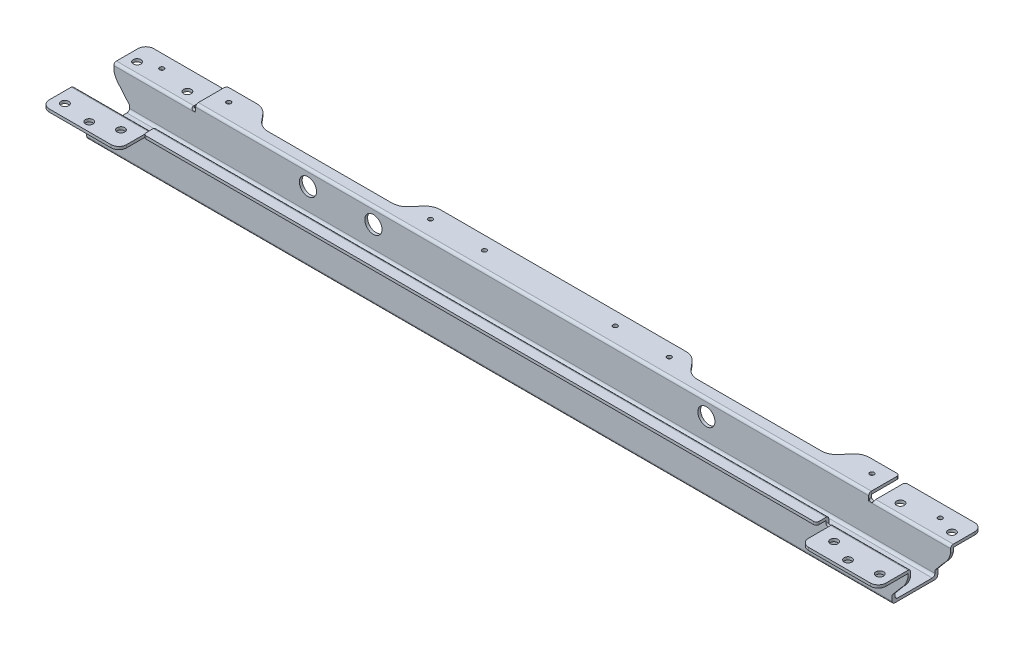
SolidWorks part; units mm, degrees
material "Plain Carbon Steel"
ref_plane "Front Plane" through (0, 0, 0) normal (0, 0, 1) x (1, 0, 0)
ref_plane "Top Plane" through (0, 0, 0) normal (0, 1, 0) x (1, 0, 0)
ref_plane "Right Plane" through (0, 0, 0) normal (1, 0, 0) x (0, 0, -1)
sketch "Sketch1" plane through (0, 0, 0) normal (1, 0, 0) x (0, 0, -1)
  line L0 (-11.095, 0) -> (11.095, 0)
  line L1 (-10.975, 4.55) -> (-10.975, 3)
  line L2 (13.7885, 0) -> (-13.7885, 0) construction
  line L3 (12.535, 1.44) -> (12.535, 4.55)
  line L4 (-12.535, 1.44) -> (-12.535, 4.55)
  line L5 (-12.535, 4.55) -> (-10.975, 4.55)
  line L6 (-9.535, 1.56) -> (9.535, 1.56)
  line L7 (10.975, 3) -> (10.975, 4.55)
  line L8 (10.975, 4.55) -> (12.535, 4.55)
  arc A0 (9.535, 1.56) -> (10.975, 3) centre (9.535, 3) ccw
  arc A1 (11.095, 0) -> (12.535, 1.44) centre (11.095, 1.44) ccw
  arc A2 (-11.095, 0) -> (-12.535, 1.44) centre (-11.095, 1.44) cw
  arc A3 (-10.975, 3) -> (-9.535, 1.56) centre (-9.535, 3) ccw
  point P4 (0, 0)
  point P17 (12.535, 0)
  dimension "D1" = 1.44
  dimension "D5" = 1.56
  dimension "D2" = 25.07
  dimension "D3" = 4.55
  dimension "D4" = 4.55
  dimension "D6" = 1.56
extrude "Boss-Extrude1" add sketch "Sketch1" against normal blind 442.65
sketch "Sketch2" plane through (0, 0, -12.535) normal (0, 0, -1) x (-1, 0, 0)
  line L0 (-8.63, 20.52) -> (-8.63, 16.92)
  line L1 (0, 2.5025) -> (0, -2.5025) construction
  line L2 (406.27, 20.52) -> (406.27, 23.26)
  line L3 (0, 20.52) -> (-8.63, 20.52)
  line L4 (0, 4.55) -> (-4.988, 10.4945)
  line L5 (442.65, 4.55) -> (0, 4.55) construction
  line L6 (0, 20.52) -> (33.94, 20.52)
  line L7 (36.38, 20.52) -> (36.38, 23.26)
  line L8 (36.38, 23.26) -> (406.27, 23.26)
  line L9 (221.325, 23.26) -> (221.325, -129.1352) construction
  line L10 (442.65, 20.52) -> (408.71, 20.52)
  line L11 (442.65, 20.52) -> (451.28, 20.52)
  line L12 (442.65, 4.55) -> (447.638, 10.4945)
  line L13 (451.28, 20.52) -> (451.28, 16.92)
  line L14 (0, 4.55) -> (442.65, 4.55)
  arc A0 (-8.63, 16.92) -> (-4.988, 10.4945) centre (2.9813, 19.2564) ccw
  arc A1 (33.94, 20.52) -> (36.38, 20.52) centre (35.16, 20.52) ccw
  arc A2 (408.71, 20.52) -> (406.27, 20.52) centre (407.49, 20.52) cw
  arc A3 (451.28, 16.92) -> (447.638, 10.4945) centre (439.6687, 19.2564) cw
  dimension "D5" = 11.844
  dimension "D7" = 1.22
  dimension "D1" = 7.76
  dimension "D2" = 3.6
  dimension "D3" = 8.63
  dimension "D4" = 130
  dimension "D6" = 42.57
  dimension "D8" = 2.74
extrude "Boss-Extrude2" add sketch "Sketch2" against normal blind 25.07
sketch "Sketch4" plane through (-451.28, 0, 0) normal (-1, 0, 0) x (0, 0, 1)
  line L1 (12.535, 23.26) -> (-12.535, 23.26) construction
  line L4 (-10.975, 23.26) -> (10.975, 23.26)
  line L5 (-10.975, 23.26) -> (-10.975, 4.55)
  line L6 (-10.975, 4.55) -> (10.975, 4.55)
  line L7 (10.975, 23.26) -> (10.975, 4.55)
extrude "Cut-Extrude2" cut sketch "Sketch4" against normal through all
sketch "Sketch5" plane through (0, 0, -12.535) normal (0, 0, -1) x (-1, 0, 0)
  line L0 (442.65, 1.44) -> (442.65, 4.55) construction
  line L2 (13.7885, 0) -> (-13.7885, 0) construction
  circle A0 centre (344.595, 14.795) radius 4.725
  circle A1 centre (308.625, 14.795) radius 4.725
  circle A2 centre (125.615, 14.795) radius 4.725
  dimension "D3" = 14.795
  dimension "D1" = 9.45
  dimension "D5" = 9.45
  dimension "D2" = 98.055
  dimension "D4" = 35.97
  dimension "D6" = 183.01
extrude "Cut-Extrude3" cut sketch "Sketch5" against normal blind 1.56
sketch "Sketch7" plane through (0, 20.52, 0) normal (0, 1, 0) x (1, 0, 0)
  line L0 (-406.27, 12.535) -> (-408.71, 12.535) construction
  line L1 (-451.28, 12.535) -> (-408.71, 12.535)
  line L2 (-451.28, 12.535) -> (-451.28, 24.245)
  line L3 (-446.96, 28.565) -> (-410.15, 28.565)
  line L4 (-408.71, 12.535) -> (-408.71, 27.125)
  line L5 (-451.28, 12.535) -> (-408.71, 12.535) construction
  line L6 (-221.325, 10.975) -> (-221.325, 60.9766) construction
  line L7 (-442.65, 10.975) -> (0, 10.975) construction
  line L8 (-33.94, 12.535) -> (-33.94, 27.125)
  line L9 (4.31, 28.565) -> (-32.5, 28.565)
  line L10 (8.63, 12.535) -> (8.63, 24.245)
  line L11 (8.63, 12.535) -> (-33.94, 12.535)
  arc A0 (-410.15, 28.565) -> (-408.71, 27.125) centre (-410.15, 27.125) cw
  arc A1 (-451.28, 24.245) -> (-446.96, 28.565) centre (-446.96, 24.245) cw
  arc A2 (-32.5, 28.565) -> (-33.94, 27.125) centre (-32.5, 27.125) ccw
  arc A3 (8.63, 24.245) -> (4.31, 28.565) centre (4.31, 24.245) ccw
  point P12 (-408.71, 28.565)
  point P15 (-451.28, 28.565)
  dimension "D3" = 1.44
  dimension "D4" = 4.32
  dimension "D1" = 16.03
  dimension "D2" = 42.57
extrude "Boss-Extrude3" add sketch "Sketch7" against normal blind 1.56
sketch "Sketch8" plane through (0, 20.52, 0) normal (0, 1, 0) x (1, 0, 0)
  line L0 (-221.325, -9.535) -> (-221.325, -77.2706) construction
  line L1 (-33.94, -12.535) -> (8.63, -12.535)
  line L2 (-33.94, -12.535) -> (-33.94, -24.515)
  line L3 (-29.62, -28.835) -> (4.31, -28.835)
  line L4 (8.63, -12.535) -> (8.63, -24.515)
  line L5 (-442.65, -9.535) -> (0, -9.535) construction
  line L6 (-408.71, -12.535) -> (-408.71, -24.515)
  line L7 (-408.71, -12.535) -> (-451.28, -12.535)
  line L8 (-451.28, -12.535) -> (-451.28, -24.515)
  line L9 (-413.03, -28.835) -> (-446.96, -28.835)
  arc A0 (4.31, -28.835) -> (8.63, -24.515) centre (4.31, -24.515) ccw
  arc A1 (-33.94, -24.515) -> (-29.62, -28.835) centre (-29.62, -24.515) ccw
  arc A2 (-446.96, -28.835) -> (-451.28, -24.515) centre (-446.96, -24.515) cw
  arc A3 (-408.71, -24.515) -> (-413.03, -28.835) centre (-413.03, -24.515) cw
  point P7 (8.63, -28.835)
  point P10 (-33.94, -28.835)
  dimension "D3" = 4.32
  dimension "D1" = 42.57
  dimension "D2" = 16.3
extrude "Boss-Extrude4" add sketch "Sketch8" against normal blind 1.56
fillet "Fillet1" radius 1.44 4 edges at (-429.995, 20.52, -10.975) (-429.995, 20.52, 10.975) (-12.655, 20.52, -10.975) (-12.655, 20.52, 10.975)
sketch "Sketch9" plane through (0, 23.26, 0) normal (0, 1, 0) x (1, 0, 0)
  line L0 (-406.27, 12.535) -> (-406.27, 26.505)
  line L1 (-406.27, -12.535) -> (-36.38, -12.535)
  line L2 (-406.27, -12.535) -> (-406.27, -16.365)
  line L3 (-404.83, -17.805) -> (-37.82, -17.805)
  line L4 (-36.38, -12.535) -> (-36.38, -16.365)
  line L5 (-404.83, 27.945) -> (-389.8589, 27.945)
  line L6 (-383.2403, 24.8587) -> (-379.9113, 20.8913)
  line L7 (-373.2926, 17.805) -> (-305.2815, 17.805)
  line L8 (-36.3803, 12.535) -> (-36.3803, 26.505)
  line L9 (-339.2871, 17.805) -> (-339.2871, 41.4911) construction
  line L10 (-37.8203, 27.945) -> (-52.7914, 27.945)
  line L11 (-295.3339, 24.8587) -> (-298.6629, 20.8913)
  line L12 (-273.7442, 27.945) -> (-288.7153, 27.945)
  line L13 (-273.7442, 27.945) -> (-168.9062, 27.945)
  line L14 (-221.3252, 27.945) -> (-221.3252, 77.3152) construction
  line L15 (-59.41, 24.8587) -> (-62.7391, 20.8913)
  line L16 (-69.3577, 17.805) -> (-137.3688, 17.805)
  line L17 (-147.3164, 24.8587) -> (-143.9874, 20.8913)
  line L18 (-168.9062, 27.945) -> (-153.9351, 27.945)
  line L19 (-406.27, 12.535) -> (-36.3803, 12.535)
  arc A0 (-37.82, -17.805) -> (-36.38, -16.365) centre (-37.82, -16.365) ccw
  arc A1 (-406.27, -16.365) -> (-404.83, -17.805) centre (-404.83, -16.365) ccw
  arc A2 (-406.27, 26.505) -> (-404.83, 27.945) centre (-404.83, 26.505) cw
  arc A3 (-389.8589, 27.945) -> (-383.2403, 24.8587) centre (-389.8589, 19.305) cw
  arc A4 (-379.9113, 20.8913) -> (-373.2926, 17.805) centre (-373.2926, 26.445) ccw
  arc A5 (-298.6629, 20.8913) -> (-305.2815, 17.805) centre (-305.2815, 26.445) cw
  arc A6 (-288.7153, 27.945) -> (-295.3339, 24.8587) centre (-288.7153, 19.305) ccw
  arc A7 (-36.3803, 26.505) -> (-37.8203, 27.945) centre (-37.8203, 26.505) ccw
  arc A8 (-52.7914, 27.945) -> (-59.41, 24.8587) centre (-52.7914, 19.305) ccw
  arc A9 (-62.7391, 20.8913) -> (-69.3577, 17.805) centre (-69.3577, 26.445) cw
  arc A10 (-143.9874, 20.8913) -> (-137.3688, 17.805) centre (-137.3688, 26.445) ccw
  arc A11 (-153.9351, 27.945) -> (-147.3164, 24.8587) centre (-153.9351, 19.305) cw
  point P7 (-36.38, -17.805)
  point P10 (-406.27, -17.805)
  dimension "D3" = 1.44
  dimension "D4" = 1.44
  dimension "D6" = 8.64
  dimension "D7" = 8.64
  dimension "D1" = 5.27
  dimension "D2" = 369.89
  dimension "D5" = 15.41
extrude "Boss-Extrude5" add sketch "Sketch9" against normal blind 1.56
fillet "Fillet2" radius 1.44 2 edges at (-221.325, 23.26, -10.975) (-221.325, 23.26, 10.975)
sketch "Sketch10" plane through (0, 20.52, 0) normal (0, 1, 0) x (1, 0, 0)
  line L0 (-410.15, 28.565) -> (-446.96, 28.565) construction
  line L1 (-221.3252, 27.945) -> (-221.3252, -55.4224) construction
  line L2 (-451.28, 12.415) -> (-451.28, 24.245) construction
  line L3 (-153.9351, 27.945) -> (-288.7153, 27.945) construction
  line L4 (-408.71, -24.515) -> (-408.71, -12.535) construction
  line L10 (-446.96, -28.835) -> (-413.03, -28.835) construction
  line L11 (-451.28, -24.515) -> (-451.28, -12.415) construction
  circle A0 centre (-445.255, 17.74) radius 2.115
  circle A1 centre (-435.24, 21.325) radius 1.22
  circle A2 centre (-417.275, 17.41) radius 2.115
  circle A3 centre (-25.3753, 17.41) radius 2.115
  circle A4 centre (-7.4103, 21.325) radius 1.22
  circle A5 centre (2.6047, 17.74) radius 2.115
  circle A7 centre (-445.255, -21.95) radius 2.115
  circle A8 centre (-429.825, -23.97) radius 2.115
  circle A9 centre (-417.295, -19.08) radius 2.115
  circle A10 centre (2.6047, -21.95) radius 2.115
  circle A11 centre (-12.8253, -23.97) radius 2.115
  circle A12 centre (-25.3553, -19.08) radius 2.115
  dimension "D3" = 4.23
  dimension "D4" = 16.04
  dimension "D6" = 11.155
  dimension "D8" = 4.23
  dimension "D11" = 6.885
  dimension "D9" = 4.23
  dimension "D14" = 4.865
  dimension "D12" = 21.455
  dimension "D17" = 8.585
  dimension "D13" = 4.23
  dimension "D15" = 4.23
  dimension "D1" = 7.24
  dimension "D2" = 10.825
  dimension "D5" = 6.025
  dimension "D7" = 34.005
  dimension "D10" = 6.025
  dimension "D16" = 9.755
extrude "Cut-Extrude4" cut sketch "Sketch10" against normal through all
sketch "Sketch11" plane through (0, 23.26, 0) normal (0, 1, 0) x (1, 0, 0)
  line L0 (-389.8589, 27.945) -> (-404.83, 27.945) construction
  line L2 (-406.27, 12.415) -> (-406.27, 26.505) construction
  line L4 (-153.9351, 27.945) -> (-288.7153, 27.945) construction
  line L5 (-221.3252, 27.945) -> (-221.3252, 64.8902) construction
  circle A0 centre (-398.07, 20.925) radius 1.22
  circle A1 centre (-286.9553, 20.675) radius 1.22
  circle A2 centre (-257.2753, 20.675) radius 1.22
  circle A3 centre (-44.5803, 20.925) radius 1.22
  circle A4 centre (-185.3751, 20.675) radius 1.22
  circle A5 centre (-155.6951, 20.675) radius 1.22
  circle A6 centre (-99.485, 0) radius 2.875
  circle A7 centre (-182.065, 0) radius 3.865
  circle A8 centre (-343.1653, 0) radius 2.875
  circle A9 centre (-260.5853, 0) radius 3.865
  dimension "D2" = 7.02
  dimension "D1" = 2.44
  dimension "D6" = 7.27
  dimension "D4" = 2.44
  dimension "D8" = 2.44
  dimension "D9" = 5.75
  dimension "D11" = 7.73
  dimension "D3" = 8.2
  dimension "D5" = 7.27
  dimension "D7" = 29.68
  dimension "D10" = 99.485
  dimension "D12" = 82.58
  dimension "D13" = 35.9501
  dimension "D14" = 35.9501
extrude "Cut-Extrude5" cut sketch "Sketch11" against normal through all
